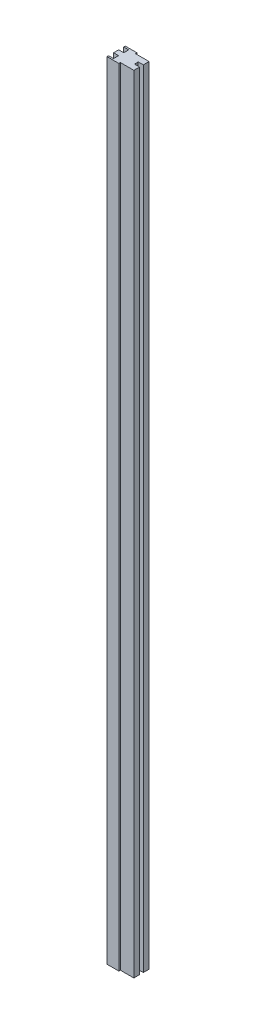
SolidWorks part; units mm, degrees
ref_plane "Спереди" through (0, 0, 0) normal (0, 0, 1) x (1, 0, 0)
ref_plane "Сверху" through (0, 0, 0) normal (0, 1, 0) x (1, 0, 0)
ref_plane "Справа" through (0, 0, 0) normal (1, 0, 0) x (0, 0, -1)
sketch "Эскиз1" plane through (0, 0, 0) normal (0, 1, 0) x (1, 0, 0)
  line L4 (-10, -14.9403) -> (-10, -5)
  line L5 (-10, -5) -> (-20, -5)
  line L6 (-20, -5) -> (-20, 0)
  line L7 (-32.4821, 0) -> (46.2952, 0) construction
  line L13 (30, -15) -> (30, -3.6855)
  line L14 (30, -3.6855) -> (20, -3.6855)
  line L15 (20, -3.6855) -> (20, 3.6855)
  line L17 (-10, -14.9403) -> (-20, -14.9403)
  line L18 (-20, -14.9403) -> (-20, -18)
  line L19 (-20, -18) -> (3.3428, -18)
  line L20 (3.3428, -18) -> (3.3428, -15)
  line L21 (3.3428, -15) -> (30, -15)
  line L22 (3.3428, 15) -> (30, 15)
  line L23 (3.3428, 18) -> (3.3428, 15)
  line L24 (-20, 18) -> (3.3428, 18)
  line L25 (-20, 14.9403) -> (-20, 18)
  line L26 (-10, 14.9403) -> (-20, 14.9403)
  line L27 (30, 3.6855) -> (20, 3.6855)
  line L28 (30, 15) -> (30, 3.6855)
  line L30 (-20, 5) -> (-20, 0)
  line L31 (-10, 5) -> (-20, 5)
  line L32 (-10, 14.9403) -> (-10, 5)
  point P9 (-32.4821, 0)
  point P10 (-18.3003, 0)
  point P21 (0, 0)
  point P24 (-22.0601, 0)
  point P25 (-19.8834, -14.9403)
  point P26 (0, 0)
  point P30 (0, 0)
  point P31 (0, 0)
  dimension "D1" = 50
extrude "Бобышка-Вытянуть1" add sketch "Эскиз1" along normal blind 1550
